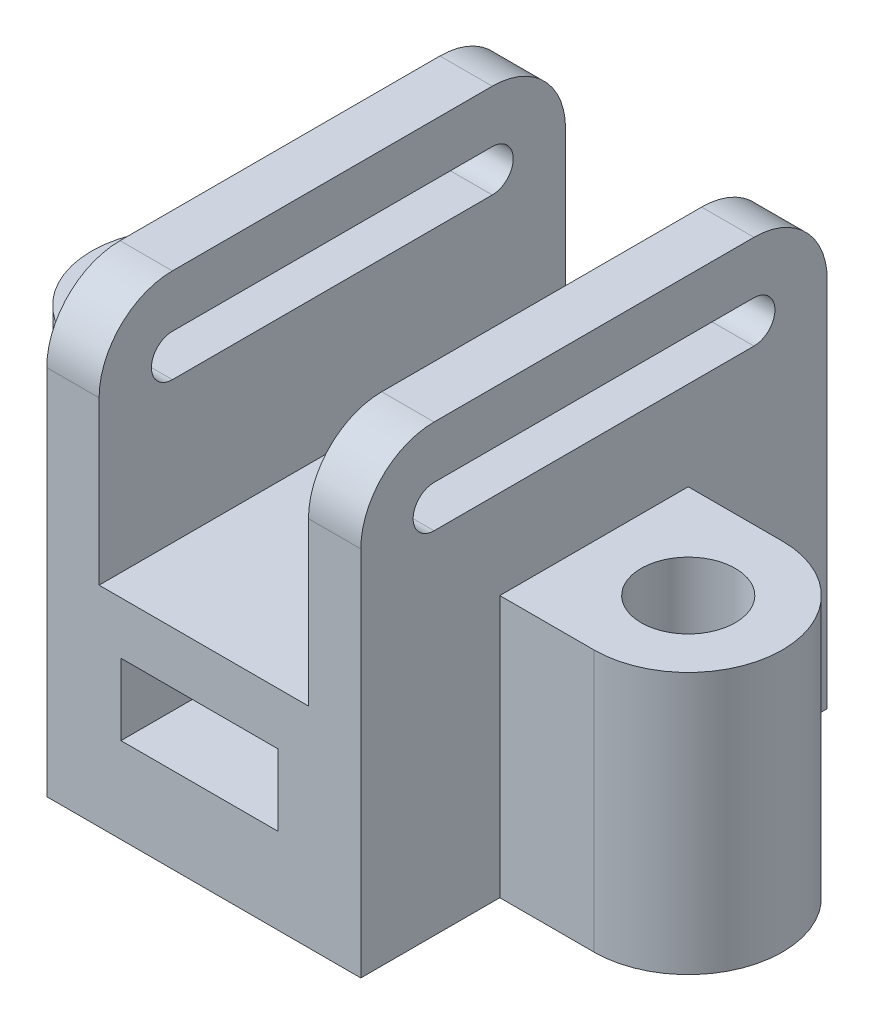
SolidWorks part; units mm, degrees
ref_plane "Front Plane" through (0, 0, 0) normal (0, 0, 1) x (1, 0, 0)
ref_plane "Top Plane" through (0, 0, 0) normal (0, 1, 0) x (1, 0, 0)
ref_plane "Right Plane" through (0, 0, 0) normal (1, 0, 0) x (0, 0, -1)
sketch "Sketch1" plane through (0, 0, 0) normal (0, 1, 0) x (1, 0, 0)
  line L0 (20, -44.56) -> (20, 44.56)
  line L9 (-10, -10) -> (10, -10)
  line L10 (-10, -10) -> (-10, 10)
  line L11 (-10, 10) -> (10, 10)
  line L12 (10, -10) -> (10, 10)
  line L13 (-10, -10) -> (10, 10) construction
  line L14 (-10, 10) -> (10, -10) construction
  line L15 (-30, -44.56) -> (30, -44.56)
  line L16 (-30, -44.56) -> (-30, 44.56)
  line L17 (-30, 44.56) -> (30, 44.56)
  line L18 (30, -44.56) -> (30, 44.56)
  line L19 (-30, -44.56) -> (30, 44.56) construction
  line L20 (-30, 44.56) -> (30, -44.56) construction
  line L21 (-20, -44.56) -> (-20, 44.56)
  line L22 (-48, 18) -> (-30, 18)
  line L23 (-48, -18) -> (-30, -18)
  line L25 (48, -18) -> (30, -18)
  line L26 (48, 18) -> (30, 18)
  arc A0 (-48, 18) -> (-48, -18) centre (-48, 0) ccw
  circle A1 centre (-48, 0) radius 9
  circle A2 centre (48, 0) radius 9
  arc A3 (48, 18) -> (48, -18) centre (48, 0) cw
  point P0 (0, 0)
  point P5 (0, 0)
  dimension "D6" = 36
  dimension "D7" = 18
  dimension "D1" = 20
  dimension "D2" = 60
  dimension "D5" = 18
  dimension "D8" = 96
  dimension "D3" = 10
  dimension "D4" = 10
extrude "Boss-Extrude1" add sketch "Sketch1" along normal blind 85 contours L15 L21 L17 L16 | L15 L18 L17 L0 region at (25, 0, 0) region at (-25, 0, 0)
extrude "Boss-Extrude2" add sketch "Sketch1<5>" along normal blind 40 contours L21 L15 L0 L17 L12 L9 L10 L11 region at (0, 0, 43.5831)
sketch "Sketch1<5>" plane through (0, 0, 0) normal (0, 1, 0) x (1, 0, 0) same geometry as "Sketch1"
extrude "Boss-Extrude3" add sketch "Sketch1<6>" along normal blind 50 contours L22 A0 L23 L16 A1 | A3 L26 L18 L25 A2 region at (30.5091, 0, 0) region at (-39, 0, 17.4909)
sketch "Sketch1<6>" plane through (0, 0, 0) normal (0, 1, 0) x (1, 0, 0) same geometry as "Sketch1"
sketch "Sketch2" plane through (0, 0, 0) normal (1, 0, 0) x (0, 0, -1)
  line L0 (-44.56, 85) -> (-44.56, 0) construction
  line L1 (-44.56, 85) -> (44.56, 85) construction
  line L2 (44.56, 85) -> (44.56, 0) construction
  line L4 (-30.56, 67) -> (30.56, 67)
  line L5 (-30.56, 75) -> (30.56, 75)
  arc A0 (-17.1436, 75) -> (-17.1436, 67) centre (-30.56, 71) ccw
  arc A1 (17.1436, 67) -> (17.1436, 75) centre (30.56, 71) ccw
  arc A2 (-30.56, 75) -> (-30.56, 67) centre (-30.56, 71) ccw
  arc A3 (30.56, 67) -> (30.56, 75) centre (30.56, 71) ccw
  dimension "D1" = 28
  dimension "D2" = 28
  dimension "D3" = 8
  dimension "D4" = 8
extrude "Cut-Extrude1" cut sketch "Sketch2" against normal mid plane 86 contours L4 A3 L5 A2 region at (0, 71, 0)
sketch "Sketch3" plane through (30, 0, 0) normal (1, 0, 0) x (0, 0, -1)
  line L0 (-44.56, 85) -> (44.56, 85) construction
  line L1 (-44.56, 85) -> (-44.56, 0) construction
  line L2 (44.56, 85) -> (44.56, 0) construction
  line L3 (-30.56, 85) -> (-44.56, 85)
  line L4 (-44.56, 85) -> (-44.56, 71)
  line L5 (30.56, 85) -> (44.56, 85)
  line L6 (44.56, 85) -> (44.56, 71)
  circle A0 centre (-30.56, 71) radius 14
  circle A1 centre (30.56, 71) radius 14
  line M11 (44.56, 0) -> (44.56, 85)
  line M12 (44.56, 85) -> (-44.56, 85)
  line M13 (-44.56, 85) -> (-44.56, 0)
extrude "Cut-Extrude2" cut sketch "Sketch3" against normal blind 86 contours A0 M12 M13 | A1 M11 M12 region at (30, 81.8728, 41.4328) region at (30, 81.8728, -41.4328)
sketch "Sketch4" plane through (0, 0, 44.56) normal (0, 0, 1) x (1, 0, 0)
  line L0 (-20, 40) -> (20, 40) construction
  line L1 (14.1798, 16.3625) -> (-15.8202, 16.3625)
  line L2 (14.1798, 16.3625) -> (14.1798, 30)
  line L3 (14.1798, 30) -> (-15.8202, 30)
  line L4 (-15.8202, 16.3625) -> (-15.8202, 30)
  line L5 (14.1798, 16.3625) -> (-15.8202, 30) construction
  line L6 (14.1798, 30) -> (-15.8202, 16.3625) construction
  point P0 (-0.8202, 23.1813)
  dimension "D1" = 30
  dimension "D2" = 10
extrude "Cut-Extrude3" cut sketch "Sketch4" against normal blind 103
